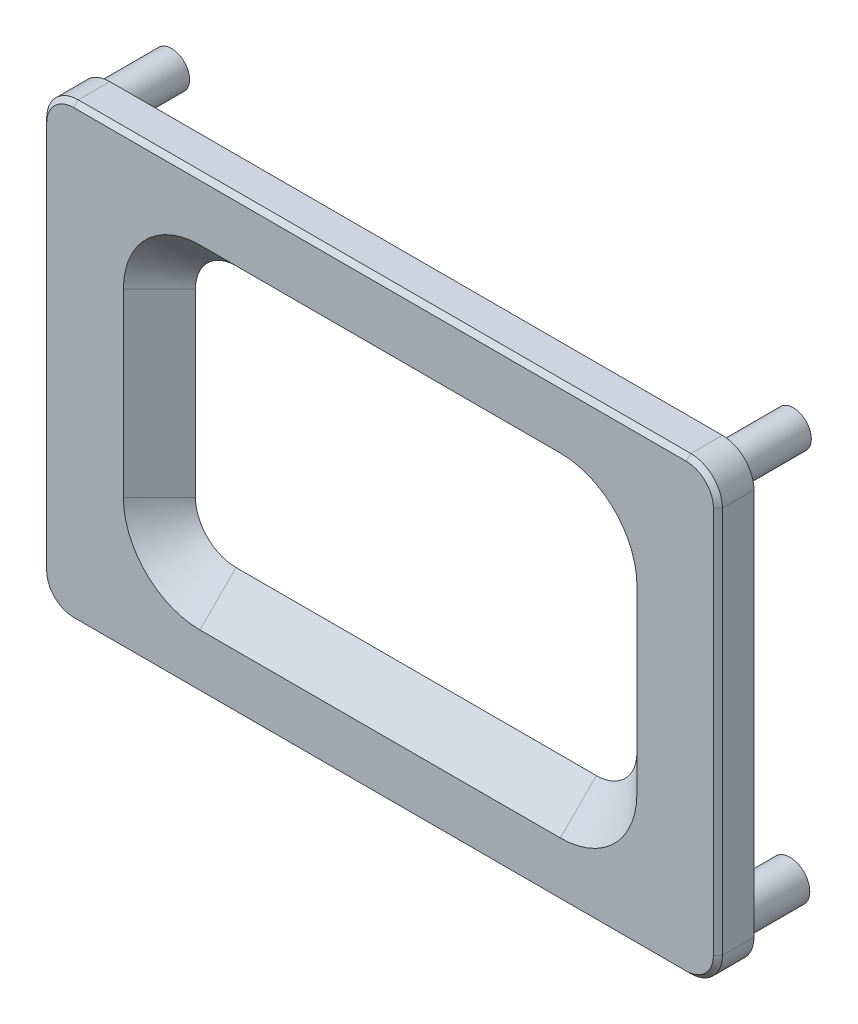
SolidWorks part; units mm, degrees
ref_plane "前视基准面" through (0, 0, 0) normal (0, 0, 1) x (1, 0, 0)
ref_plane "上视基准面" through (0, 0, 0) normal (0, 1, 0) x (1, 0, 0)
ref_plane "右视基准面" through (0, 0, 0) normal (1, 0, 0) x (0, 0, -1)
other "Configuration Table"
sketch "草图1" plane through (0, 0, 0) normal (0, 0, 1) x (1, 0, 0)
  line L1 (-44.3203, 53.2647) -> (91.6797, 53.2647)
  line L2 (-51.3203, 46.2647) -> (-51.3203, -39.7353)
  line L3 (-44.3203, -46.7353) -> (91.6797, -46.7353)
  line L4 (98.6797, 46.2647) -> (98.6797, -39.7353)
  arc A0 (-51.3203, -39.7353) -> (-44.3203, -46.7353) centre (-44.3203, -39.7353) ccw
  arc A1 (91.6797, -46.7353) -> (98.6797, -39.7353) centre (91.6797, -39.7353) ccw
  arc A2 (91.6797, 53.2647) -> (98.6797, 46.2647) centre (91.6797, 46.2647) cw
  arc A3 (-44.3203, 53.2647) -> (-51.3203, 46.2647) centre (-44.3203, 46.2647) ccw
  dimension "D1" = 7
extrude "凸台-拉伸1" add sketch "草图1" along normal blind 8
sketch "草图2" plane through (0, 0, 8) normal (0, 0, 1) x (1, 0, 0)
  line L1 (-16.2951, 29.8649) -> (63.7049, 29.8649)
  line L2 (-23.2951, 22.8649) -> (-23.2951, -17.1351)
  line L3 (-16.2951, -24.1351) -> (63.7049, -24.1351)
  line L4 (70.7049, 22.8649) -> (70.7049, -17.1351)
  arc A0 (-23.2951, -17.1351) -> (-16.2951, -24.1351) centre (-16.2951, -17.1351) ccw
  arc A1 (63.7049, -24.1351) -> (70.7049, -17.1351) centre (63.7049, -17.1351) ccw
  arc A2 (63.7049, 29.8649) -> (70.7049, 22.8649) centre (63.7049, 22.8649) cw
  arc A3 (-16.2951, 29.8649) -> (-23.2951, 22.8649) centre (-16.2951, 22.8649) ccw
  dimension "D1" = 7
extrude "切除-拉伸1" cut sketch "草图2" against normal blind 8
chamfer "倒角2" distance 1 angle 45 8 edges at (-49.27, -44.685, 8) (23.6797, -46.7353, 8) (96.6295, -44.685, 8) (98.6797, 3.2647, 8) (96.6295, 51.2144, 8) (23.6797, 53.2647, 8) (-49.27, 51.2144, 8) (-51.3203, 3.2647, 8)
sketch "草图3" plane through (0, 0, 0) normal (0, 0, -1) x (-1, 0, 0)
  circle A0 centre (-92.4172, 47.4432) radius 4
  circle A1 centre (-92.4172, 47.4432) radius 2
extrude "凸台-拉伸3" add sketch "草图3" along normal blind 15
sketch "草图5" plane through (0, 0, 0) normal (0, 0, -1) x (-1, 0, 0)
  circle A0 centre (-91.6797, -39.7353) radius 4.3964
  circle A1 centre (-91.6797, -39.7353) radius 2
extrude "凸台-拉伸4" add sketch "草图5" along normal blind 15
sketch "草图9" plane through (0, 0, 0) normal (0, 0, -1) x (-1, 0, 0)
  circle A0 centre (45.5966, 47.5002) radius 4
  circle A1 centre (45.5966, 47.5002) radius 2
extrude "凸台-拉伸5" add sketch "草图9" along normal blind 15
sketch "草图10" plane through (0, 0, 0) normal (0, 0, -1) x (-1, 0, 0)
  circle A0 centre (42.7198, -38.5359) radius 4
  circle A1 centre (42.7198, -38.5359) radius 2
extrude "凸台-拉伸6" add sketch "草图10" along normal blind 15
chamfer "倒角6" distance 10 angle 45 8 edges at (23.7049, -24.1351, 8) (68.6547, -22.0848, 8) (70.7049, 2.8649, 8) (68.6547, 27.8147, 8) (-21.2448, -22.0848, 8) (-23.2951, 2.8649, 8) (-21.2448, 27.8147, 8) (23.7049, 29.8649, 8)
